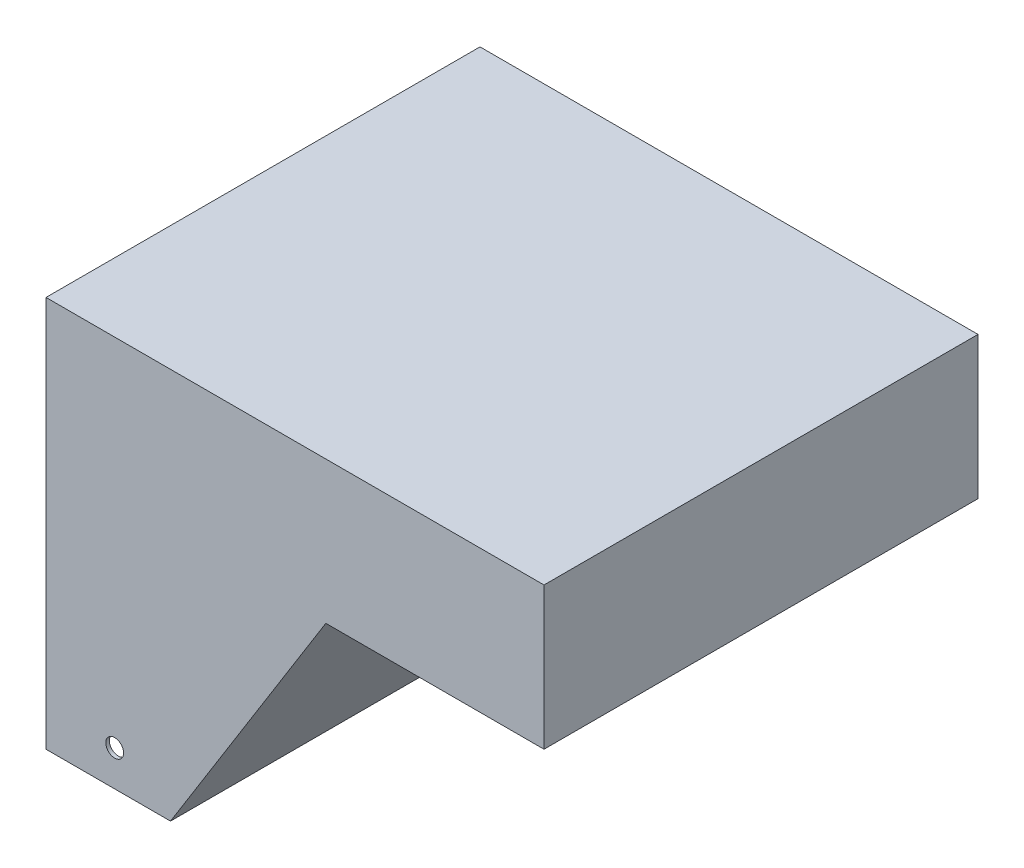
SolidWorks part; units mm, degrees
material "Acrylic (Medium-high impact)"
ref_plane "Front Plane" through (0, 0, 0) normal (0, 0, 1) x (1, 0, 0)
ref_plane "Top Plane" through (0, 0, 0) normal (0, 1, 0) x (1, 0, 0)
ref_plane "Right Plane" through (0, 0, 0) normal (1, 0, 0) x (0, 0, -1)
sketch "Sketch2" plane through (0, 0, 0) normal (0, 0, 1) x (1, 0, 0)
  line L0 (0, 0) -> (355.6, 0)
  line L1 (355.6, 0) -> (355.6, -101.6)
  line L2 (355.6, -101.6) -> (199.8078, -101.6)
  line L3 (199.8078, -101.6) -> (88.9, -279.4)
  line L4 (88.9, -279.4) -> (0, -279.4)
  line L5 (0, -279.4) -> (0, 0)
  circle A0 centre (49.0381, -254) radius 6.35
  dimension "D6" = 12.7
  dimension "D1" = 355.6
  dimension "D2" = 279.4
  dimension "D3" = 101.6
  dimension "D4" = 88.9
  dimension "D5" = 25.4
extrude "Boss-Extrude1" add sketch "Sketch2" along normal blind 2.54
sketch "Sketch3" plane through (0, 0, 2.54) normal (0, 0, 1) x (1, 0, 0)
  line L6 (2.54, -276.86) -> (2.54, -279.4)
  line L7 (0, -279.4) -> (88.9, -279.4) construction
  line L8 (87.4908, -276.86) -> (87.4908, -279.4)
  line L12 (2.54, -2.54) -> (2.54, -276.86)
  line L13 (2.54, -276.86) -> (87.4908, -276.86)
  line L14 (87.4908, -276.86) -> (198.3986, -99.06)
  line L15 (198.3986, -99.06) -> (353.06, -99.06)
  line L16 (353.06, -99.06) -> (353.06, -2.54)
  line L17 (353.06, -2.54) -> (2.54, -2.54)
  line L18 (2.54, -2.54) -> (2.54, -276.86)
  line L20 (87.4908, -276.86) -> (198.3986, -99.06)
  line L21 (198.3986, -99.06) -> (353.06, -99.06)
  line L22 (353.06, -99.06) -> (353.06, -2.54)
  line L23 (353.06, -2.54) -> (2.54, -2.54)
  line M7 (0, 0) -> (0, -279.4)
  line M8 (0, -279.4) -> (88.9, -279.4)
  line M9 (88.9, -279.4) -> (199.8078, -101.6)
  line M10 (199.8078, -101.6) -> (355.6, -101.6)
  line M11 (355.6, -101.6) -> (355.6, 0)
  line M12 (355.6, 0) -> (0, 0)
  dimension "D1" = 2.54
extrude "Boss-Extrude2" add sketch "Sketch3" along normal blind 304.8 contours L23 L22 L21 L20 L18 M12 M7 M8 M9 M10 M11 region at (2.0878, -278.13, 2.54)
ref_plane "Plane1" through (0, 0, 154.94) normal (0, 0, 1) x (1, 0, 0)
mirror "Mirror1" about plane through (0, 0, 154.94) normal (0, 0, 1) of "Boss-Extrude1"
sketch "Sketch4" plane through (0, 0, 0) normal (-1, 0, 0) x (0, 0, 1)
  line L0 (309.88, -279.4) -> (0, -279.4) construction
  line L1 (120.015, -244.851) -> (189.865, -244.851) construction
  circle A0 centre (120.015, -244.851) radius 1.5875
  circle A1 centre (120.015, -270.251) radius 1.5875
  circle A2 centre (189.865, -244.851) radius 1.5875
  circle A3 centre (189.865, -270.251) radius 1.5875
  point P8 (154.94, -279.4)
  point P9 (154.94, -244.851)
  point P12 (0, 0)
  point P13 (0, 0)
  point P14 (0, 0)
  point P15 (0, 0)
  point P16 (120.015, -222.1787)
  dimension "D1" = 3.175
  dimension "D2" = 69.85
  dimension "D3" = 25.4
extrude "Cut-Extrude1" cut sketch "Sketch4" against normal up to next
